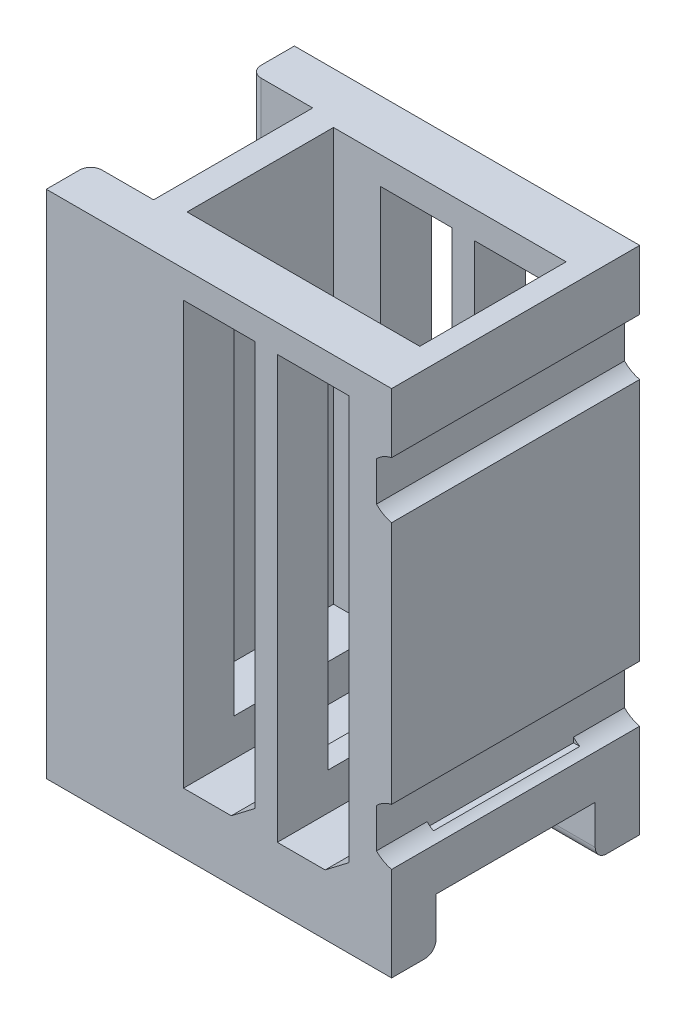
SolidWorks part; units mm, degrees
ref_plane "Front Plane" through (0, 0, 0) normal (0, 0, 1) x (1, 0, 0)
ref_plane "Top Plane" through (0, 0, 0) normal (0, 1, 0) x (1, 0, 0)
ref_plane "Right Plane" through (0, 0, 0) normal (1, 0, 0) x (0, 0, -1)
sketch "Sketch1" plane through (0, 0, 0) normal (0, 1, 0) x (1, 0, 0)
  line L0 (31, 0) -> (31, 19.5)
  line L1 (0, 0) -> (31, 0)
  line L2 (0, 0) -> (0, 19.5)
  line L3 (0, 19.5) -> (31, 19.5)
  line L4 (31, 0) -> (31, 19.5)
  line L5 (31, 9.75) -> (31, 23.2966) construction
  line L6 (31, 9.75) -> (31, -3.75)
  line L7 (31, -3.75) -> (34, -3.75)
  line L8 (34, -3.75) -> (34, 23.2966)
  line L9 (34, 23.2966) -> (31, 23.2966)
  line L10 (34, 23.2966) -> (34, 26.2966)
  line L11 (34, -3.75) -> (34, -6.75)
  line L12 (34, -6.75) -> (-12, -6.75)
  line L13 (-12, -6.75) -> (-12, 26.2966)
  line L14 (-12, 26.2966) -> (34, 26.2966)
  point P5 (31, 9.75)
  dimension "D1" = 31
  dimension "D2" = 19.5
extrude "Boss-Extrude1" add sketch "Sketch1" along normal blind 55 contours L3 L5 L9 L10 L14 L13 L12 L11 L7 L6 L1 L2 | L5 L4 L0 L6 L7 L8 L9
sketch "Sketch2" plane through (0, 0, 6.75) normal (0, 0, 1) x (1, 0, 0)
  line L0 (34, 0) -> (34, -13)
  line L1 (34, -13) -> (-12, -13)
  line L2 (-12, -13) -> (-12, 0)
  line L3 (-12, 0) -> (34, 0)
extrude "Boss-Extrude2" add sketch "Sketch2" against normal up to surface (33.0466 mm away) up to face at (11, 27.5, -26.2966)
sketch "Sketch3" plane through (34, 0, 0) normal (1, 0, 0) x (0, 0, -1)
  line L0 (-6.75, -13) -> (9.7733, -13)
  line L1 (26.2966, -13) -> (-6.75, -13) construction
  line L2 (-0.8267, -13) -> (20.3733, -13)
  line L3 (20.3733, -13) -> (20.3733, -6.2834)
  line L4 (20.3733, -6.2834) -> (-0.8267, -6.2834)
  line L5 (-0.8267, -6.2834) -> (-0.8267, -13)
  point P8 (9.7733, -13)
  line M2 (-6.75, -13) -> (26.2966, -13)
extrude "Cut-Extrude1" cut sketch "Sketch3" against normal through all contours L4 L5 L0 L3 M2
sketch "Sketch4" plane through (0, 55, 0) normal (0, 1, 0) x (1, 0, 0)
  line L0 (-12, 9.7733) -> (-12, 20.3733)
  line L1 (-12, -6.75) -> (-12, 26.2966) construction
  line L2 (-12, 20.3733) -> (-6.6321, 20.3733)
  line L3 (-6.6321, 20.3733) -> (-6.6321, -0.8267)
  line L4 (-6.6321, -0.8267) -> (-12, -0.8267)
  line L5 (-12, -0.8267) -> (-12, 9.7733)
  line L6 (-6.6321, 20.3733) -> (-3.6321, 20.3733)
  line L7 (-3.6321, 20.3733) -> (-3.6321, -0.8267)
  line L8 (-3.6321, -0.8267) -> (-6.6321, -0.8267)
  line M11 (-12, 26.2966) -> (-12, -6.75)
extrude "Cut-Extrude2" cut sketch "Sketch4" against normal through all contours L8 L7 L6 L3 | L4 L3 L2 M11
sketch "Sketch5" plane through (0, 0, 6.75) normal (0, 0, 1) x (1, 0, 0)
  line L0 (28.3252, 51.3318) -> (18.7735, 51.3318)
  line L1 (18.7735, 51.3318) -> (18.7735, 44.0156)
  line L3 (28.3252, 51.3318) -> (28.3252, -2.5237)
  line L4 (28.3252, -2.5237) -> (18.7735, -9.8399)
  line L5 (18.7735, -9.8399) -> (18.7735, 44.0156)
  line L6 (6.2735, -9.8399) -> (6.2735, 44.0156)
  line L7 (6.2735, 51.3318) -> (6.2735, 44.0156)
  line L8 (15.8252, 51.3318) -> (6.2735, 51.3318)
  line L9 (15.8252, 51.3318) -> (15.8252, -2.5237)
  line L10 (15.8252, -2.5237) -> (6.2735, -9.8399)
  line L16 (-6.2265, -9.8399) -> (-6.2265, 44.0156) [skipped]
  line L17 (3.3252, 51.3318) -> (3.3252, -2.5237) [skipped]
  line L18 (3.3252, 51.3318) -> (-6.2265, 51.3318) [skipped]
  line L19 (-6.2265, 51.3318) -> (-6.2265, 44.0156) [skipped]
  line L20 (3.3252, -2.5237) -> (-6.2265, -9.8399) [skipped]
  dimension "D1" = 3
extrude "Cut-Extrude5" cut sketch "Sketch5" against normal blind 55
sketch "Sketch6" plane through (0, 0, 6.75) normal (0, 0, 1) x (1, 0, 0)
  line L0 (32.8979, -4.9624) -> (3.633, -4.9624)
  line L1 (3.633, -4.9624) -> (3.633, -11.2625)
  line L2 (3.633, -11.2625) -> (32.8979, -11.2625)
  line L3 (32.8979, -11.2625) -> (32.8979, -4.9624)
extrude "Boss-Extrude3" add sketch "Sketch6" against normal up to surface (33.0466 mm away)
sketch "Sketch7" plane through (34, 0, 0) normal (1, 0, 0) x (0, 0, -1)
  line L0 (20.3733, -6.2834) -> (20.3733, -13)
  line L1 (20.3733, -13) -> (-0.8267, -13)
  line L2 (-0.8267, -13) -> (-0.8267, -6.2834)
  line L3 (-0.8267, -6.2834) -> (20.3733, -6.2834)
extrude "Cut-Extrude6" cut sketch "Sketch7" against normal through all
sketch "Sketch8" plane through (0, 0, 6.75) normal (0, 0, 1) x (1, 0, 0)
  line L0 (34, 7.028) -> (30.8656, 7.028)
  line L1 (34, 55) -> (34, -13) construction
  line L2 (30.8656, 7.028) -> (30.8656, -0.472)
  line L3 (30.8656, -0.472) -> (34, -0.472)
  line L4 (34, -0.472) -> (34, 7.028)
  line L5 (34, 39.528) -> (34, 47.028)
  line L6 (30.8656, 47.028) -> (30.8656, 39.528)
  line L7 (30.8656, 39.528) -> (34, 39.528)
  line L8 (34, 47.028) -> (30.8656, 47.028)
  dimension "D1" = 2
extrude "Cut-Extrude7" cut sketch "Sketch8" against normal blind 55
fillet "Fillet1" radius 4 4 edges at (30.8656, -0.472, -9.7733) (30.8656, 39.528, -22.8983) (30.8656, 7.028, -22.8983) (30.8656, 47.028, 3.375)
sketch "Sketch9" plane through (0, 0, 6.75) normal (0, 0, 1) x (1, 0, 0)
  line L0 (31.9833, 50.4173) -> (31.9833, -4.1495)
  line L1 (31.9833, -4.1495) -> (30.2559, -4.1495)
  line L2 (30.2559, -4.1495) -> (30.2559, 50.4173)
  line L3 (30.2559, 50.4173) -> (31.9833, 50.4173)
extrude "Boss-Extrude4" add sketch "Sketch9" against normal up to surface (33.0466 mm away)
sketch "Sketch10" plane through (0, 55, 0) normal (0, 1, 0) x (1, 0, 0)
  line L0 (30.2559, 19.5) -> (31, 19.5)
  line L1 (31, 19.5) -> (31, 0)
  line L2 (31, 0) -> (30.2559, 0)
  line L3 (30.2559, 0) -> (30.2559, 19.5)
extrude "Cut-Extrude8" cut sketch "Sketch10" against normal up to surface (59.9624 mm away) up to face at (21.9574, -4.9624, -9.7733)
sketch "Sketch11" plane through (0, 55, 0) normal (0, 1, 0) x (1, 0, 0)
  line L0 (28.3252, 19.5) -> (31, 19.5)
  line L1 (31, 19.5) -> (31, 0)
  line L2 (31, 0) -> (28.3252, 0)
  line L3 (28.3252, 0) -> (28.3252, 19.5)
fillet "Fillet2" radius 1.5 4 edges at (-12, 21, -20.3733) (-12, 21, 0.8267) (11, -13, 0.8267) (11, -13, -20.3733)
